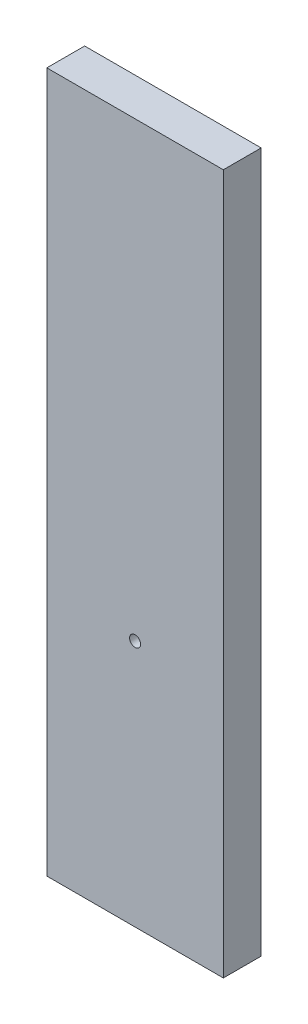
SolidWorks part; units mm, degrees
ref_plane "Front Plane" through (0, 0, 0) normal (0, 0, 1) x (1, 0, 0)
ref_plane "Top Plane" through (0, 0, 0) normal (0, 1, 0) x (1, 0, 0)
ref_plane "Right Plane" through (0, 0, 0) normal (1, 0, 0) x (0, 0, -1)
sketch "Sketch1" plane through (0, 0, 0) normal (0, 1, 0) x (1, 0, 0)
  line L1 (0, 0) -> (88.9, 0)
  line L2 (0, 0) -> (0, 19.05)
  line L3 (0, 19.05) -> (88.9, 19.05)
  line L4 (88.9, 0) -> (88.9, 19.05)
  dimension "D1" = 19.05
  dimension "D2" = 88.9
extrude "Boss-Extrude1" add sketch "Sketch1" along normal blind 352.522
sketch "Sketch2" plane through (0, 0, 0) normal (0, 0, 1) x (1, 0, 0)
  line L0 (44.45, 352.522) -> (44.45, 124.7234) construction
  line L1 (0, 352.522) -> (88.9, 352.522) construction
  line L2 (-349.25, 173.0637) -> (44.45, 124.7234) construction
  line L3 (-349.25, 173.0637) -> (-39.4224, 173.0637) construction
  circle A0 centre (44.45, 124.7234) radius 2.7781
  circle A1 centre (-349.25, 173.0637) radius 2.7781 construction
  circle A2 centre (-349.25, 173.0637) radius 2.7781 construction
  dimension "D1" = 5.5562
  dimension "D2" = 7
extrude "Cut-Extrude1" cut sketch "Sketch2" against normal through all
equation "\"DROPANGLE\"= 10"
